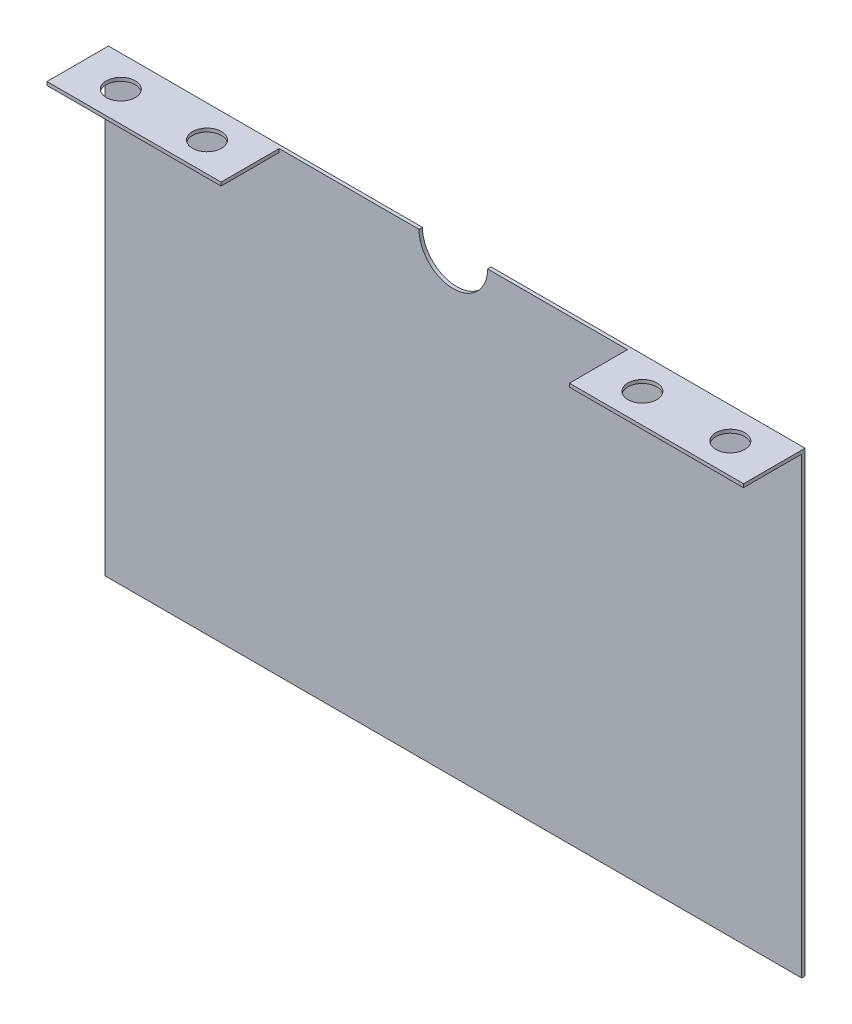
SolidWorks part; units mm, degrees
ref_plane "Front Plane" through (0, 0, 0) normal (0, 0, 1) x (1, 0, 0)
ref_plane "Top Plane" through (0, 0, 0) normal (0, 1, 0) x (1, 0, 0)
ref_plane "Right Plane" through (0, 0, 0) normal (1, 0, 0) x (0, 0, -1)
sketch "Sketch1" plane through (0, 0, 0) normal (0, 0, 1) x (1, 0, 0)
  line L0 (0, 0) -> (0, 100) construction
  line L1 (-152.4, 100) -> (-15, 100)
  line L2 (-152.4, 100) -> (-152.4, -100)
  line L3 (-152.4, -100) -> (152.4, -100)
  line L4 (152.4, 100) -> (152.4, -100)
  line L5 (-152.4, 0) -> (152.4, 0) construction
  line L6 (15, 100) -> (152.4, 100)
  line L7 (-15, 100) -> (15, 100) construction
  arc A0 (15, 100) -> (-15, 100) centre (0, 100) cw
  dimension "D3" = 15
  dimension "D1" = 304.8
  dimension "D2" = 200
  dimension "D4" = 152.4
extrude "Bottom Center Casing" add sketch "Sketch1" along normal blind 1.5189
sketch "Sketch2" plane through (0, 0, 1.5189) normal (0, 0, 1) x (1, 0, 0)
  line L0 (-15, 100) -> (-152.4, 100) construction
  line L1 (152.4, 100) -> (15, 100) construction
  line L2 (0, 100) -> (0, 66.7) construction
  line L3 (-83.7, 100) -> (83.7, 100) construction
  point P0 (-83.7, 100)
  point P3 (-83.7, 100)
  point P4 (83.7, 100)
  point P7 (83.7, 100)
  point P12 (0, 100)
  dimension "D1" = 33.3
sketch "Sketch3" plane through (0, 0, 1.5189) normal (0, 0, 1) x (1, 0, 0)
  line L1 (-152.4, 100) -> (-76.2, 100)
  line L2 (-152.4, 100) -> (-152.4, 98.4811)
  line L3 (-152.4, 98.4811) -> (-76.2, 98.4811)
  line L4 (-76.2, 100) -> (-76.2, 98.4811)
  line L5 (152.4, 100) -> (76.2, 100)
  line L6 (152.4, 100) -> (152.4, 98.4811)
  line L7 (152.4, 98.4811) -> (76.2, 98.4811)
  line L8 (76.2, 100) -> (76.2, 98.4811)
  dimension "D1" = 76.2
  dimension "D2" = 1.5189
  dimension "D3" = 1.5189
  dimension "D4" = 76.2
extrude "Boss-Extrude1" add sketch "Sketch3" along normal blind 25.4
sketch "Sketch4" plane through (0, 100, 0) normal (0, 1, 0) x (1, 0, 0)
  line L0 (-152.4, -13.4595) -> (-76.2, -14.2189) construction
  line L1 (-152.4, -26.9189) -> (-152.4, 0) construction
  line L2 (-76.2, -26.9189) -> (-76.2, -1.5189) construction
  line L4 (0, -14.8054) -> (0, 14.8054) construction
  circle A0 centre (-133.35, -13.6493) radius 6.35
  circle A1 centre (-95.25, -14.0291) radius 6.35
  circle A2 centre (95.25, -14.0291) radius 6.35
  circle A3 centre (133.35, -13.6493) radius 6.35
  point P10 (0, 0)
  point P12 (-153.6488, 2.2894)
  dimension "D1" = 12.7
  dimension "D2" = 19.05
  dimension "D3" = 38.1
extrude "Cut-Extrude1" cut sketch "Sketch4" against normal blind 25.4
